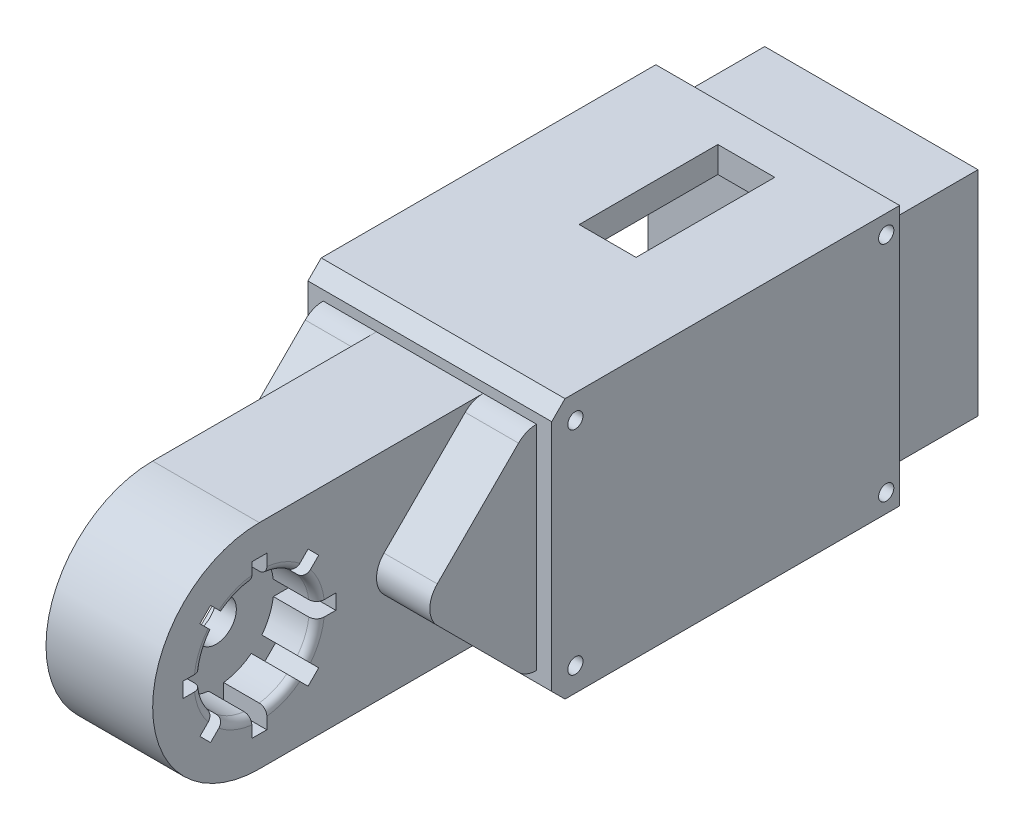
SolidWorks part; units mm, degrees
ref_plane "Front Plane" through (0, 0, 0) normal (0, 0, 1) x (1, 0, 0)
ref_plane "Top Plane" through (0, 0, 0) normal (0, 1, 0) x (1, 0, 0)
ref_plane "Right Plane" through (0, 0, 0) normal (1, 0, 0) x (0, 0, -1)
sketch "Sketch2" plane through (0, 0, 0) normal (0, 0, 1) x (1, 0, 0)
  line L1 (-21, 21) -> (21, 21)
  line L2 (-21, 21) -> (-21, -21)
  line L3 (-21, -21) -> (21, -21)
  line L4 (21, 21) -> (21, -21)
  line L5 (-21, 21) -> (21, -21) construction
  line L6 (-21, -21) -> (21, 21) construction
  point P0 (0, 0)
  dimension "D1" = 42
  dimension "D2" = 42
extrude "Boss-Extrude1" add sketch "Sketch2" along normal blind 89
ref_plane "Plane1" through (0, 0, 89) normal (0, 0, 1) x (1, 0, 0)
sketch "Sketch3" plane through (0, 0, 89) normal (0, 0, 1) x (1, 0, 0)
  line L0 (21, 21) -> (-21, 21) construction
  line L1 (10.5, -21) -> (-10.5, -21)
  line L2 (10.5, -21) -> (10.5, 21)
  line L3 (10.5, 21) -> (-10.5, 21)
  line L4 (-10.5, -21) -> (-10.5, 21)
  line L5 (10.5, -21) -> (-10.5, 21) construction
  line L6 (10.5, 21) -> (-10.5, -21) construction
  point P0 (0, 0)
  dimension "D1" = 21
ref_plane "Plane4" through (0, 0, 0) normal (0, 0, -1) x (-1, 0, 0)
extrude "Boss-Extrude2" add sketch "Sketch3" along normal blind 42
ref_plane "Plane5" through (-10.5, 0, 0) normal (-1, 0, 0) x (0, 0, 1)
sketch "Sketch8" plane through (-10.5, 0, 0) normal (-1, 0, 0) x (0, 0, 1)
  line L0 (131, 21) -> (131, -21) construction
  line L1 (131, 21) -> (131, -21)
  arc A0 (131, 21) -> (131, -21) centre (131, 0) cw
  dimension "D1" = 21
extrude "Boss-Extrude3" add sketch "Sketch8" against normal blind 21
ref_plane "Plane6" through (-10.5, 0, 0) normal (-1, 0, 0) x (0, 0, 1)
sketch "Sketch9" plane through (-10.5, 0, 0) normal (-1, 0, 0) x (0, 0, 1)
  line L0 (89, 21) -> (89, -21) construction
  line L1 (131, 21) -> (131, -21)
  circle A0 centre (131, 0) radius 11.35
  dimension "D1" = 42
  dimension "D2" = 22.7
extrude "Cut-Extrude2" cut sketch "Sketch9" against normal blind 8.5 contours A0
ref_plane "Plane7" through (10.5, 0, 0) normal (1, 0, 0) x (0, 0, -1)
sketch "Sketch11" plane through (10.5, 0, 0) normal (1, 0, 0) x (0, 0, -1)
  line L0 (-131, 21) -> (-131, -21)
  circle A0 centre (-131, 0) radius 11.35
  dimension "D1" = 22.7
extrude "Cut-Extrude3" cut sketch "Sketch11" against normal blind 8.5 contours A0
ref_plane "Plane8" through (-2, 0, 0) normal (-1, 0, 0) x (0, 0, 1)
sketch "Sketch12" plane through (-2, 0, 0) normal (-1, 0, 0) x (0, 0, 1)
  circle A0 centre (131, 0) radius 3.975
  dimension "D1" = 7.95
extrude "Cut-Extrude4" cut sketch "Sketch12" against normal through all
ref_plane "Plane10" through (-2, 0, 0) normal (-1, 0, 0) x (0, 0, 1)
ref_plane "Plane11" through (-10.5, 0, 0) normal (-1, 0, 0) x (0, 0, 1)
sketch "Sketch20" plane through (-10.5, 0, 0) normal (-1, 0, 0) x (0, 0, 1)
  line L0 (131, 0) -> (110, 0)
  line L1 (110, 0) -> (110, 21)
  line L2 (110, 0) -> (110, -21)
  line L4 (110, 21) -> (89, 21)
  line L6 (110, -21) -> (89, -21)
  line L7 (89, 21) -> (110, 0)
  line L8 (89, -21) -> (110, 0)
  line L9 (89, 21) -> (89, -21)
  circle A0 centre (131, 0) radius 11.35
  dimension "D1" = 21
extrude "Boss-Extrude4" add sketch "Sketch20" along normal blind 10.5 and the other way blind 31.5 contours L7 L9 L8 region at (-10.5, 0, 96)
fillet "Fillet1" radius 5 1 edges at (15.75, 0, 110)
fillet "Fillet2" radius 5 1 edges at (-15.75, 0, 110)
fillet "Fillet3" radius 5 1 edges at (-15.75, -21, 89)
fillet "Fillet4" radius 5 1 edges at (-15.75, 21, 89)
fillet "Fillet5" radius 5 1 edges at (15.75, -21, 89)
fillet "Fillet6" radius 5 1 edges at (15.75, 21, 89)
fillet "Fillet7" radius 1.5 1 edges at (-10.5, 0, 142.35)
fillet "Fillet8" radius 1.5 1 edges at (10.5, 0, 119.65)
sketch "Sketch21" plane through (-10.5, 0, 0) normal (-1, 0, 0) x (0, 0, 1)
  line L1 (129.5207, 10.6415) -> (132.4793, 10.6415)
  line L2 (129.5207, 10.6415) -> (129.5207, 15.0585)
  line L3 (129.5207, 15.0585) -> (132.4793, 15.0585)
  line L4 (132.4793, 10.6415) -> (132.4793, 15.0585)
  line L5 (129.5207, 10.6415) -> (132.4793, 15.0585) construction
  line L6 (129.5207, 15.0585) -> (132.4793, 10.6415) construction
  circle A0 centre (131, 0) radius 12.85 construction
  point P0 (131, 12.85)
  dimension "D1" = 4.417
extrude "Cut-Extrude5" cut sketch "Sketch21" against normal blind 8.5
pattern_circular "CirPattern2" count 8 over 360 about axis through (-9, 0, 131) along (-1, 0, 0) of "Cut-Extrude5"
ref_plane "Plane12" through (0, 21, 0) normal (0, 1, 0) x (1, 0, 0)
ref_plane "Plane13" through (10.5, 0, 0) normal (1, 0, 0) x (0, 0, -1)
ref_plane "Plane14" through (0, 0, 0) normal (1, 0, 0) x (0, 0, -1)
mirror "Mirror1" about plane through (0, 0, 0) normal (1, 0, 0) of "CirPattern2"
ref_plane "Plane15" through (21, 0, 0) normal (1, 0, 0) x (0, 0, -1)
sketch "Sketch24" plane through (21, 0, 0) normal (1, 0, 0) x (0, 0, -1)
  line L1 (-86.9289, 21) -> (0, 21)
  line L2 (-86.9289, 21) -> (-86.9289, 25.5452)
  line L3 (-86.9289, 25.5452) -> (0, 25.5452)
  line L4 (0, 21) -> (0, 25.5452)
  line L5 (-86.9289, -21) -> (0, -21)
  line L6 (-86.9289, -21) -> (-86.9289, -25.6891)
  line L7 (-86.9289, -25.6891) -> (0, -25.6891)
  line L8 (0, -21) -> (0, -25.6891)
extrude "Boss-Extrude6" add sketch "Sketch24" against normal blind 42
sketch "Sketch25" plane through (21, 0, 0) normal (1, 0, 0) x (0, 0, -1)
  line L0 (-18.4289, -25.6891) -> (-18.4289, 25.5452)
  line L1 (-86.9289, 25.5452) -> (-18.4289, 25.5452)
  line L2 (-86.9289, 25.5452) -> (-86.9289, -25.6891)
  line L3 (-86.9289, -25.6891) -> (-18.4289, -25.6891)
  dimension "D1" = 68.5
extrude "Boss-Extrude7" add sketch "Sketch25" along normal blind 3
ref_plane "Plane18" through (0, 0, 0) normal (0, 0, -1) x (-1, 0, 0)
ref_plane "Plane19" through (-21, 0, 0) normal (-1, 0, 0) x (0, 0, 1)
sketch "Sketch28" plane through (-21, 0, 0) normal (-1, 0, 0) x (0, 0, 1)
  line L0 (86.9289, -25.6891) -> (0, -25.6891) construction
  line L1 (86.9289, 25.5452) -> (18.4289, 25.5452)
  line L2 (86.9289, 25.5452) -> (86.9289, -25.6891)
  line L3 (86.9289, -25.6891) -> (18.4289, -25.6891)
  line L4 (18.4289, 25.5452) -> (18.4289, -25.6891)
  dimension "D1" = 68.5
extrude "Boss-Extrude8" add sketch "Sketch28" along normal blind 3
ref_plane "Plane20" through (-24, 0, 0) normal (-1, 0, 0) x (0, 0, 1)
sketch "Sketch30" plane through (-24, 0, 0) normal (-1, 0, 0) x (0, 0, 1)
  line L1 (81.9289, 20.4302) -> (19.9289, 20.4302)
  line L2 (81.9289, 20.4302) -> (81.9289, -20.5741)
  line L3 (81.9289, -20.5741) -> (19.9289, -20.5741)
  line L4 (19.9289, 20.4302) -> (19.9289, -20.5741)
  line L5 (81.9289, 20.4302) -> (19.9289, -20.5741) construction
  line L6 (81.9289, -20.5741) -> (19.9289, 20.4302) construction
  line L8 (86.9289, 25.5452) -> (18.4289, 25.5452) construction
  line L9 (18.4289, -25.6891) -> (86.9289, -25.6891) construction
  line L10 (86.9289, -21) -> (86.9289, 21) construction
  point P0 (50.9289, -0.0719)
  dimension "D1" = 5.115
  dimension "D2" = 5.115
  dimension "D3" = 62
  dimension "D4" = 5
extrude "Cut-Extrude6" cut sketch "Sketch30" against normal blind 45
ref_plane "Plane21" through (21, 0, 0) normal (1, 0, 0) x (0, 0, -1)
sketch "Sketch31" plane through (21, 0, 0) normal (1, 0, 0) x (0, 0, -1)
  line L0 (0, -25.6891) -> (0, 25.5452) construction
  line L1 (-18.4289, -25.6891) -> (0, -25.6891)
  line L2 (-18.4289, -25.6891) -> (-18.4289, -21.0741)
  line L3 (-18.4289, -21.0741) -> (0, -21.0741)
  line L4 (0, -25.6891) -> (0, -21.0741)
  line L6 (-18.4289, 25.5452) -> (0, 25.5452)
  line L7 (-18.4289, 25.5452) -> (-18.4289, 20.9302)
  line L8 (-18.4289, 20.9302) -> (0, 20.9302)
  line L9 (0, 25.5452) -> (0, 20.9302)
  dimension "D1" = 4.615
  dimension "D2" = 4.615
extrude "Cut-Extrude7" cut sketch "Sketch31" against normal through all
chamfer "Chamfer1" distance 1.5 angle 45 4 edges at (0, 20.9302, 18.4289) (21, -0.0719, 18.4289) (0, -21.0741, 18.4289) (-21, -0.0719, 18.4289)
ref_plane "Plane22" through (0, 0, 0) normal (0, 0, -1) x (-1, 0, 0)
sketch "Sketch32" plane through (0, 0, 0) normal (0, 0, -1) x (-1, 0, 0)
  line L1 (15, 15) -> (-15, 15)
  line L2 (15, 15) -> (15, -15)
  line L3 (15, -15) -> (-15, -15)
  line L4 (-15, 15) -> (-15, -15)
  line L5 (15, 15) -> (-15, -15) construction
  line L6 (15, -15) -> (-15, 15) construction
  point P0 (0, 0)
  dimension "D1" = 30
  dimension "D2" = 30
extrude "Cut-Extrude8" cut sketch "Sketch32" against normal blind 16.8
ref_plane "Plane23" through (0, 0, 19.9289) normal (0, 0, 1) x (1, 0, 0)
sketch "Sketch33" plane through (0, 0, 19.9289) normal (0, 0, 1) x (1, 0, 0)
  circle A0 centre (0, 0) radius 5
  dimension "D1" = 10
extrude "Cut-Extrude9" cut sketch "Sketch33" against normal blind 16.8
ref_plane "Plane24" through (-21, 0, 0) normal (-1, 0, 0) x (0, 0, 1)
sketch "Sketch34" plane through (-24, 0, 0) normal (-1, 0, 0) x (0, 0, 1)
  line L0 (86.9289, -0.0719) -> (103.6427, -0.0719) construction
  line L2 (88.3304, -21.6696) -> (88.3304, -28.2221)
  line L3 (88.3304, -28.2221) -> (81.7779, -28.2221)
  line L4 (81.7779, -28.2221) -> (88.3304, -21.6696)
  line L5 (86.9289, -25.6891) -> (86.9289, 25.5452) construction
  line L6 (88.3304, 28.0782) -> (81.7779, 28.0782)
  line L7 (88.3304, 21.5257) -> (88.3304, 28.0782)
  line L8 (81.7779, 28.0782) -> (88.3304, 21.5257)
extrude "Cut-Extrude10" cut sketch "Sketch34" against normal through all
chamfer "Chamfer2" distance 6 angle 45 1 edges at (-1.5, 20.4302, 81.9289)
chamfer "Chamfer3" distance 6 angle 45 1 edges at (-1.5, -20.5741, 81.9289)
chamfer "Chamfer4" distance 6 angle 45 1 edges at (-1.5, 20.4302, 19.9289)
chamfer "Chamfer5" distance 6 angle 45 1 edges at (-1.5, -20.5741, 19.9289)
sketch "Sketch35" plane through (-24, 0, 0) normal (-1, 0, 0) x (0, 0, 1)
  line L0 (78.9289, -17.5741) -> (85.6199, -24.3801) construction
  line L1 (82.2744, 20.8332) -> (85.6199, 24.2362) construction
  line L2 (81.9289, -14.5741) -> (75.9289, -20.5741) construction
  line L3 (84.3109, -25.6891) -> (86.9289, -23.0711) construction
  line L4 (78.9289, 17.4302) -> (85.6199, 24.2362) construction
  line L5 (75.9289, 20.4302) -> (81.9289, 14.4302) construction
  line L6 (86.9289, 22.9272) -> (84.3109, 25.5452) construction
  line L7 (18.4289, 25.5452) -> (21.0741, 21.9048) construction
  line L9 (18.4289, -25.6891) -> (21.074, -22.0485) construction
  line L10 (18.4289, 25.5452) -> (18.4289, -25.6891) construction
  circle A0 centre (21.0741, 21.9048) radius 1.5
  circle A1 centre (82.2744, 20.8332) radius 1.5
  circle A2 centre (82.2744, -20.9771) radius 1.5
  circle A3 centre (21.074, -22.0485) radius 1.5
  dimension "D5" = 3
  dimension "D1" = 36.003
  dimension "D2" = 36
  dimension "D3" = 4.5
  dimension "D4" = 4.5
extrude "Cut-Extrude11" cut sketch "Sketch35" against normal through all
ref_plane "Plane26" through (0, -25.6891, 0) normal (0, -1, 0) x (-1, 0, 0)
sketch "Sketch38" plane through (0, -25.6891, 0) normal (0, -1, 0) x (-1, 0, 0)
  line L0 (-24, -18.4289) -> (24, -18.4289) construction
  line L1 (4.2922, -53.2289) -> (-6.9078, -53.2289)
  line L2 (4.2922, -53.2289) -> (4.2922, -25.9289)
  line L3 (4.2922, -25.9289) -> (-6.9078, -25.9289)
  line L4 (-6.9078, -53.2289) -> (-6.9078, -25.9289)
  dimension "D1" = 7.5
  dimension "D2" = 27.3
  dimension "D3" = 11.2
extrude "Cut-Extrude12" cut sketch "Sketch38" against normal through all
